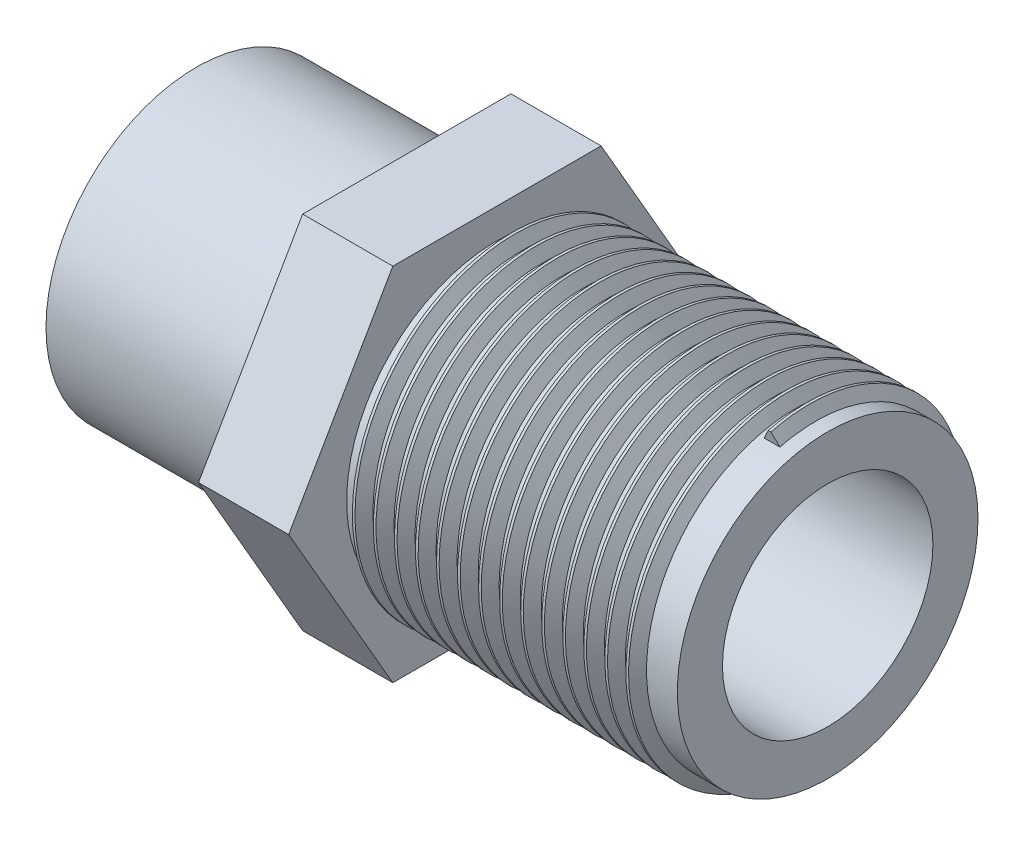
SolidWorks part; units mm, degrees
ref_plane "Front Plane" through (0, 0, 0) normal (0, 0, 1) x (1, 0, 0)
ref_plane "Top Plane" through (0, 0, 0) normal (0, 1, 0) x (1, 0, 0)
ref_plane "Right Plane" through (0, 0, 0) normal (1, 0, 0) x (0, 0, -1)
sketch "Sketch1" plane through (0, 0, 0) normal (1, 0, 0) x (0, 0, -1)
  circle A0 centre (0, 0) radius 5
  circle A1 centre (0, 0) radius 3.5
  dimension "D1" = 7
  dimension "D2" = 10
extrude "Boss-Extrude1" add sketch "Sketch1" along normal mid plane 11
sketch "Sketch2" plane through (-5.5, 0, 0) normal (-1, 0, 0) x (0, 0, 1)
  line L1 (6.9282, 0) -> (3.4641, 6)
  line L2 (3.4641, 6) -> (-3.4641, 6)
  line L3 (-3.4641, 6) -> (-6.9282, 0)
  line L4 (-6.9282, 0) -> (-3.4641, -6)
  line L5 (-3.4641, -6) -> (3.4641, -6)
  line L6 (3.4641, -6) -> (6.9282, 0)
  circle A0 centre (0, 0) radius 6 construction
  circle A1 centre (0, 0) radius 5 construction
  dimension "D1" = 12
extrude "Boss-Extrude2" add sketch "Sketch2" along normal blind 3
sketch "Sketch3" plane through (-8.5, 0, 0) normal (-1, 0, 0) x (0, 0, 1)
  circle A0 centre (0, 0) radius 5
  dimension "D1" = 10
extrude "Boss-Extrude3" add sketch "Sketch3" along normal blind 7
sketch "Sketch4" plane through (-15.5, 0, 0) normal (-1, 0, 0) x (0, 0, 1)
  circle A0 centre (0, 0) radius 3.5
  circle A1 centre (0, 0) radius 5 construction
  dimension "D1" = 7
extrude "Cut-Extrude1" cut sketch "Sketch4" against normal up to next
thread "Thread1" pitch 0.7 method extrude profile "Thread Profile1" start angle 0, offset 0, length 10, pitch 0.7, diameter 10
ref_plane "Plane1" through (-5.5, 0, -5) normal (0, -1, 0) x (0, 0, -1)
sketch "Thread Profile1" plane through (-5.5, 0, -5) normal (0, -1, 0) x (0, 0, -1)
  line L0 (0, 0) -> (0, 0.7) construction
  line L1 (0, 0) -> (0.3789, 0.2187)
  line L2 (0.3789, 0.2187) -> (0.3789, 0.3062)
  line L3 (0.3789, 0.3062) -> (0, 0.525)
  line L4 (0.3789, 0.2625) -> (0, 0.2625) construction
  line L11 (0, 0) -> (0, 0.525)
  point P2 (0, 0)
  dimension "Pitch" = 0.7
  dimension "Profile_Angle" = 60
  dimension "Profile_Land" = 0.0875
  dimension "Profile_Height" = 0.3789
